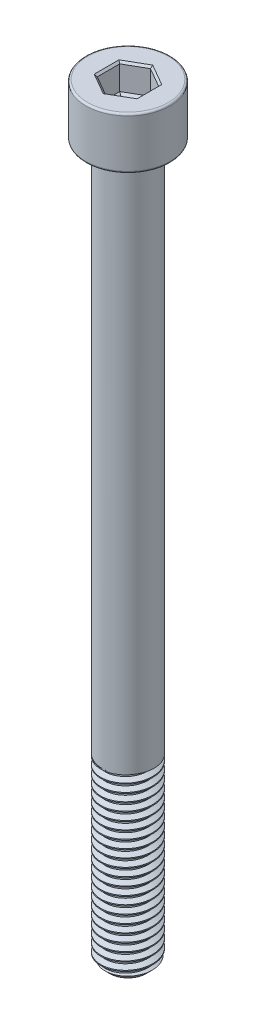
SolidWorks part; units mm, degrees
material "AISI Type A2 Tool Steel"
ref_plane "Front Plane" through (0, 0, 0) normal (0, 0, 1) x (1, 0, 0)
ref_plane "Top Plane" through (0, 0, 0) normal (0, 1, 0) x (1, 0, 0)
ref_plane "Right Plane" through (0, 0, 0) normal (1, 0, 0) x (0, 0, -1)
sketch "Sketch1" plane through (0, 0, 0) normal (0, 1, 0) x (1, 0, 0)
  circle A0 centre (0, 0) radius 4
  dimension "D1" = 8
extrude "Boss-Extrude1" add sketch "Sketch1" along normal blind 28
thread "Thread1" pitch 1.25 method cut profile "Thread Profile1" start angle 0, offset 2, length 0, pitch 1.25, diameter 8
ref_plane "Plane1" through (-4, 30, 0) normal (0, 0, 1) x (-1, 0, 0)
sketch "Thread Profile1" plane through (-4, 30, 0) normal (0, 0, 1) x (-1, 0, 0)
  line L0 (0, 0) -> (0, 1.25) construction
  line L11 (0, 0) -> (0, 1.0937)
  line L12 (0, 1.0937) -> (-0.6766, 0.7031)
  line L13 (-0.6766, 0.7031) -> (-0.6766, 0.3906)
  line L15 (-0.6766, 0.3906) -> (0, 0)
  line L17 (-0.6766, 0.5469) -> (0, 0.5469) construction
  point P2 (0, 0)
  dimension "Pitch" = 1.25
  dimension "Profile_Angle" = 60
  dimension "Profile_Land" = 0.3125
  dimension "Profile_Height" = 0.6766
sketch "Sketch2" plane through (0, 28, 0) normal (0, 1, 0) x (1, 0, 0)
  circle A0 centre (0, 0) radius 4
  dimension "D1" = 8
extrude "Boss-Extrude2" add sketch "Sketch2" along normal blind 82
sketch "Sketch5" plane through (0, 110, 0) normal (0, 1, 0) x (1, 0, 0)
  circle A0 centre (0, 0) radius 6.5
  dimension "D1" = 13
extrude "Boss-Extrude3" add sketch "Sketch5" along normal blind 8
sketch "Sketch6" plane through (0, 0, 0) normal (0, 0, 1) x (1, 0, 0)
  line L0 (0, 0) -> (0, 0.7245) construction
  line L1 (0, 0) -> (4.01, 0) construction
  line L2 (4.01, 0) -> (4.01, 1.2)
  line L3 (4.01, 1.2) -> (2.81, 0)
  line L4 (2.81, 0) -> (4.01, 0)
  dimension "D1" = 1.2
  dimension "D2" = 45
  dimension "D3" = 4.01
revolve "Cut-Revolve1" cut sketch "Sketch6" angle 360 about L0
fillet "Fillet1" radius 0.3 2 edges at (0, 110, 6.5) (0, 118, 6.5)
sketch "Sketch7" plane through (0, 118, 0) normal (0, 1, 0) x (1, 0, 0)
  line L1 (0, 3.4641) -> (-3, 1.7321)
  line L2 (-3, 1.7321) -> (-3, -1.7321)
  line L3 (-3, -1.7321) -> (0, -3.4641)
  line L4 (0, -3.4641) -> (3, -1.7321)
  line L5 (3, -1.7321) -> (3, 1.7321)
  line L6 (3, 1.7321) -> (0, 3.4641)
  circle A0 centre (0, 0) radius 3 construction
  dimension "D1" = 6
extrude "Cut-Extrude1" cut sketch "Sketch7" against normal blind 4
chamfer "Chamfer1" distance 0.3 angle 45 6 edges at (-3, 118, 0) (-1.5, 118, 2.5981) (1.5, 118, 2.5981) (3, 118, 0) (1.5, 118, -2.5981) (-1.5, 118, -2.5981)
sketch "Sketch8" plane through (0, 114, 0) normal (0, 1, 0) x (1, 0, 0)
  line L1 (0, 3.4641) -> (-3, 1.7321)
  line L2 (-3, 1.7321) -> (-3, -1.7321)
  line L3 (-3, -1.7321) -> (0, -3.4641)
  line L4 (0, -3.4641) -> (3, -1.7321)
  line L5 (3, -1.7321) -> (3, 1.7321)
  line L6 (3, 1.7321) -> (0, 3.4641)
  circle A0 centre (0, 0) radius 3 construction
extrude "Cut-Extrude2" cut sketch "Sketch8" against normal blind 0.4 draft 60
